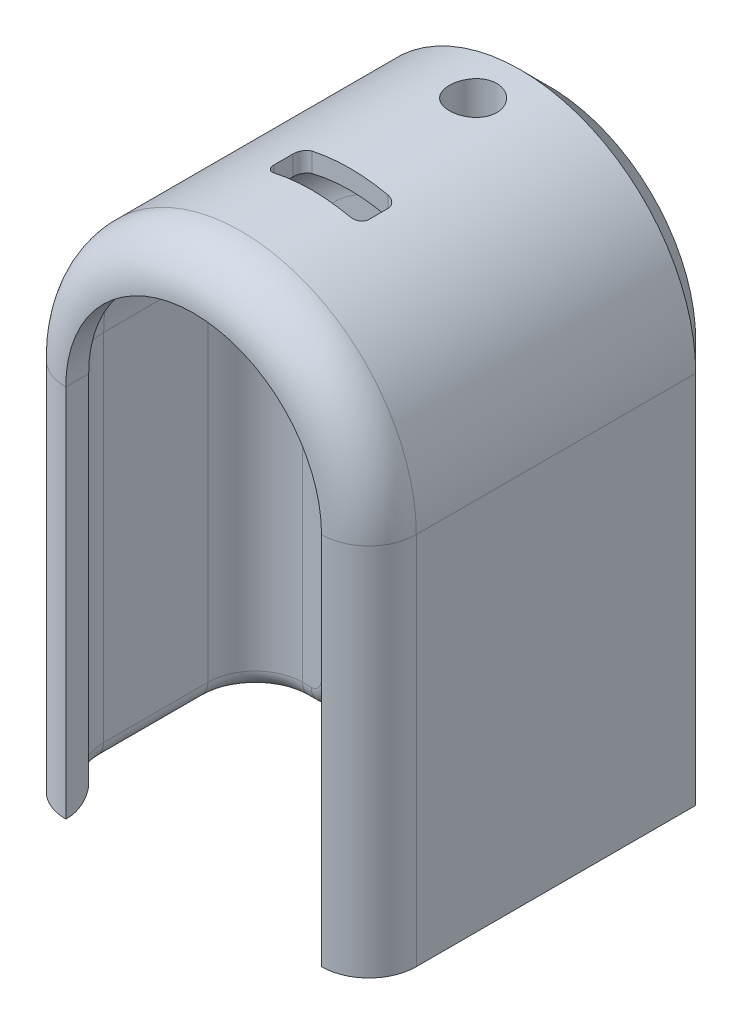
SolidWorks part; units mm, degrees
ref_plane "Plan de face" through (0, 0, 0) normal (0, 0, 1) x (1, 0, 0)
ref_plane "Plan de dessus" through (0, 0, 0) normal (0, 1, 0) x (1, 0, 0)
ref_plane "Plan de droite" through (0, 0, 0) normal (1, 0, 0) x (0, 0, -1)
sketch "Esquisse1" plane through (0, 0, 0) normal (0, 0, 1) x (1, 0, 0)
  line L1 (0, 0) -> (33, 0)
  line L2 (0, 0) -> (0, 39.5)
  line L3 (0, 39.5) -> (33, 39.5)
  line L4 (33, 0) -> (33, 39.5)
  circle A0 centre (16.5, 39.5) radius 16.5
  dimension "D1" = 33
  dimension "D2" = 39.5
extrude "Boss.-Extru.1" add sketch "Esquisse1" along normal blind 21 contours L3 A0 | L3 A0 | A0 L2 L1 L4
shell "Coque2" thickness 2
fillet "Congé1" radius 5 6 edges at (33, 19.75, 0) (0, 19.75, 0) (33, 19.75, 21) (0, 19.75, 21) (16.5, 56, 0) (16.5, 56, 21)
sketch "Esquisse2" plane through (0, 0, 23) normal (0, 0, 1) x (1, 0, 0)
  line L0 (35, 0) -> (35, 39.5) construction
  line L1 (-2, 0) -> (-2, 39.5) construction
  line L2 (35, 0) -> (35, 39.5)
  line L3 (-2, 0) -> (-2, 39.5)
  line L4 (3, 0) -> (3, 39.5)
  line L5 (30, 0) -> (30, 39.5)
  line L6 (3, 0) -> (30, 0)
  arc A0 (35, 39.5) -> (-2, 39.5) centre (16.5, 39.5) ccw construction
  arc A1 (35, 39.5) -> (-2, 39.5) centre (16.5, 39.5) ccw
  arc A2 (30, 39.5) -> (3, 39.5) centre (16.5, 39.5) ccw
  line M4 (-2, 0) -> (35, 0)
  dimension "D1" = 5
extrude "Enlèv. mat.-Extru.1" cut sketch "Esquisse2" against normal blind 10 contours L5 A2 L4 M4
fillet "Congé3" radius 5 3 edges at (35, 19.75, 23) (16.5, 58, 23) (-2, 19.75, 23)
sketch "Esquisse3" plane through (0, 0, -2) normal (0, 0, -1) x (-1, 0, 0)
  line L0 (-16.5, 15) -> (-16.5, 14) construction
  line L1 (-11.4973, 15) -> (-11.4973, 14)
  line L2 (-21.5027, 15) -> (-21.5027, 14)
  line L3 (-16.5, 26.5) -> (-16.5, 27.5) construction
  line L4 (-21.5, 26.5) -> (-21.5, 27.5)
  line L5 (-11.5, 26.5) -> (-11.5, 27.5)
  circle A0 centre (-16.5, 26.5) radius 5
  circle A1 centre (-16.5, 15) radius 5
  arc A2 (0, 39.5) -> (-33, 39.5) centre (-16.5, 39.5) ccw construction
  arc A3 (-11.4973, 15) -> (-21.5027, 15) centre (-16.5, 15) ccw
  arc A4 (-21.5027, 14) -> (-11.4973, 14) centre (-16.5, 14) ccw
  arc A5 (-21.5, 26.5) -> (-11.5, 26.5) centre (-16.5, 26.5) ccw
  arc A6 (-11.5, 27.5) -> (-21.5, 27.5) centre (-16.5, 27.5) ccw
  point P7 (-16.5, 56)
  point P8 (-16.5, 14.5)
  point P9 (-16.5, 15)
  point P10 (-16.5, 26.5)
  point P16 (-16.5, 27)
  dimension "D1" = 10
  dimension "D2" = 10
  dimension "D5" = 5
  dimension "D6" = 1
  dimension "D3" = 29.5
  dimension "D4" = 11.5
  dimension "D7" = 1
extrude "Enlèv. mat.-Extru.2" cut sketch "Esquisse3" against normal blind 10 contours L2 A4 L1 A3 A1 | A0 | L5 A6 L4 A0
sketch "Esquisse4" plane through (0, 0, 0) normal (0, -1, 0) x (-1, 0, 0)
  line L1 (-11.5, -10.5) -> (-21.5, -10.5)
  line L2 (-11.5, -10.5) -> (-11.5, -6.5)
  line L3 (-11.5, -6.5) -> (-21.5, -6.5)
  line L4 (-21.5, -10.5) -> (-21.5, -6.5)
  line L5 (-30, -23) -> (-3, -23) construction
  point P4 (-16.5, -10.5)
  point P7 (-16.5, -23)
  point P12 (-35.1083, -10.5)
  point P13 (-35.1083, -10.5)
  dimension "D1" = 4
  dimension "D2" = 10
  dimension "D3" = 0
extrude "Enlèv. mat.-Extru.4" cut sketch "Esquisse4" against normal through all
fillet "Congé5" radius 1 4 edges at (21.5, 56.2678, 6.5) (11.5, 56.2678, 10.5) (11.5, 56.2678, 6.5) (21.5, 56.2678, 10.5)
sketch "Esquisse6" plane through (0, 0, -2) normal (0, 0, -1) x (-1, 0, 0)
  line L0 (2, 0) -> (-35, 0) construction
  circle A0 centre (-16.5, 0) radius 8
  dimension "D1" = 16
extrude "Enlèv. mat.-Extru.6" cut sketch "Esquisse6" against normal blind 10
fillet "Congé7" radius 3 2 edges at (8.5, 0, -1) (24.5, 0, -1)
fillet "Congé8" radius 2 11 edges at (0.8167, 0, 18.7386) (32.1833, 0, 18.7386) (33, 0, 10.5) (31.5355, 0, 1.4645) (25.2739, 0.6068, 0) (16.5, 8, 0) (7.7261, 0.6068, 0) (1.4645, 0, 1.4645) (0, 0, 10.5) (27.5415, 0, 0) (5.4585, 0, 0)
sketch "Esquisse15" plane through (0, 0, -2) normal (0, 0, -1) x (-1, 0, 0)
  line L0 (2, 14.2) -> (-1.4, 14.2)
  line L1 (-1.4, 14.2) -> (-1.4, 9.4)
  line L2 (-1.4, 9.4) -> (-4.2, 9.4)
  line L3 (-4.2, 9.4) -> (-4.2, 14.2)
  line L4 (-4.2, 14.2) -> (-11.4973, 14.2)
  line L5 (-11.4973, 15) -> (-11.4973, 14) construction
  line L6 (-28, 0) -> (-27.083, 0)
  line L7 (-5.917, 0) -> (-5, 0)
  line L8 (-5, 0) -> (2, 0)
  line L9 (2, 0) -> (2, 39.5)
  line L10 (-35, 39.5) -> (-35, 0)
  line L11 (-35, 0) -> (-28, 0)
  line L12 (-28, 0) -> (-27.083, 0)
  line L13 (-5.917, 0) -> (-5, 0)
  line L14 (-5, 0) -> (2, 0)
  line L15 (2, 14.2) -> (2, 0)
  line L16 (-35, 39.5) -> (-35, 0)
  line L17 (-35, 0) -> (-28, 0)
  line L18 (-11.4973, 14) -> (-11.4973, 14.2)
  line L19 (-21.5027, 14) -> (-21.5, 27)
  line L20 (-8.6, 32.5) -> (-8.6, 37.1)
  line L21 (2, 37.1) -> (2, 14.2) construction
  line L22 (-8.6, 37.1) -> (-4.2, 37.1)
  line L23 (-4.2, 37.1) -> (-4.2, 41.9)
  line L24 (-4.2, 41.9) -> (-1.35, 41.9)
  line L25 (-1.35, 41.9) -> (-1.35, 37.1)
  line L26 (-1.35, 37.1) -> (2, 37.1)
  line L27 (2, 39.5) -> (2, 37.1)
  line L28 (-21.5, 26.5) -> (-21.5, 27.5) construction
  line L29 (-8.6, 32.5) -> (-16.5, 32.5)
  line L30 (-21.5, 27) -> (-21.5, 27.5)
  arc A0 (-21.5027, 14) -> (-11.4973, 14) centre (-16.5, 14) ccw construction
  arc A1 (-21.5027, 14) -> (-11.4973, 14) centre (-16.5, 14) ccw
  arc A2 (-11.5, 27.5) -> (-21.5, 27.5) centre (-16.5, 27.5) ccw construction
  arc A3 (-11.5, 27.5) -> (-21.5, 27.5) centre (-16.5, 27.5) ccw
  arc A4 (-27.083, 0) -> (-24.1967, 2.1818) centre (-27.083, 3) ccw
  arc A5 (-27.083, 0) -> (-24.1967, 2.1818) centre (-27.083, 3) ccw
  arc A6 (-8.8033, 2.1818) -> (-5.917, 0) centre (-5.917, 3) ccw
  arc A7 (2, 39.5) -> (-35, 39.5) centre (-16.5, 39.5) ccw
  arc A8 (-8.8033, 2.1818) -> (-24.1967, 2.1818) centre (-16.5, 0) ccw
  arc A9 (-8.8033, 2.1818) -> (-24.1967, 2.1818) centre (-16.5, 0) ccw
  arc A10 (-8.8033, 2.1818) -> (-5.917, 0) centre (-5.917, 3) ccw
  arc A11 (2, 39.5) -> (-35, 39.5) centre (-16.5, 39.5) ccw
  point P23 (-21.5013, 20.5)
  dimension "D2" = 4.4
  dimension "D3" = 3.4
  dimension "D4" = 2.8
  dimension "D5" = 4.8
  dimension "D6" = 0
  dimension "D7" = 6.3
  dimension "D8" = 22.9
  dimension "D9" = 4.8
  dimension "D10" = 2.85
  dimension "D11" = 4.8
  dimension "D14" = 3.35
  dimension "D1" = 0
extrude "Boss.-Extru.4" add sketch "Esquisse15" along normal blind 12.5
sketch "Esquisse16" plane through (-2, 0, 0) normal (-1, 0, 0) x (0, 0, 1)
  circle A0 centre (-8.1, 39.75) radius 1
  circle A1 centre (-8.1, 11.7639) radius 1
  dimension "D1" = 2
  dimension "D2" = 2
extrude "Enlèv. mat.-Extru.7" cut sketch "Esquisse16" against normal blind 9
sketch "Esquisse17" plane through (-2, 0, 0) normal (-1, 0, 0) x (0, 0, 1)
  circle A0 centre (-8.1, 11.7639) radius 1.5
  circle A1 centre (-8.1, 39.75) radius 1.5
  dimension "D1" = 3
  dimension "D2" = 3
extrude "Enlèv. mat.-Extru.8" cut sketch "Esquisse17" against normal blind 2
sketch "Esquisse18" plane through (0, 0, -14.5) normal (0, 0, -1) x (-1, 0, 0)
  line L1 (-31.5012, 10.341) -> (-23.5012, 10.341)
  line L2 (-31.5012, 10.341) -> (-31.5012, 41.341)
  line L3 (-31.5012, 41.341) -> (-23.5012, 41.341)
  line L4 (-23.5012, 10.341) -> (-23.5012, 41.341)
  line L5 (-21.5024, 15.0463) -> (-21.5, 27) construction
  point P6 (-21.5012, 21.0231)
  point P7 (-23.5012, 25.841)
  dimension "D1" = 31
  dimension "D2" = 8
  dimension "D3" = 2
  dimension "D4" = 0
extrude "Enlèv. mat.-Extru.9" cut sketch "Esquisse18" against normal blind 14
sketch "Esquisse19" plane through (0, 0, 0) normal (0, -1, 0) x (-1, 0, 0)
  line L0 (-35, 14.5) -> (-27.083, 14.5) construction
  line L1 (-28.5012, 14.5) -> (-30.5012, 14.5)
  line L2 (-28.5012, 14.5) -> (-28.5012, 4.5)
  line L3 (-28.5012, 4.5) -> (-30.5012, 4.5)
  line L4 (-30.5012, 14.5) -> (-30.5012, 4.5)
  line L5 (-31.5012, 14.5) -> (-23.5012, 14.5) construction
  point P6 (-29.5012, 14.5)
  point P9 (-27.5012, 14.5)
  dimension "D1" = 2
  dimension "D2" = 2
  dimension "D3" = 10
chamfer "Chanfrein1" distance 3 angle 45 4 edges at (-2, 38.3, -14.5) (16.5, 58, -14.5) (35, 19.75, -14.5) (-2, 7.1, -14.5)
sketch "Esquisse21" plane through (0, 0, -14.5) normal (0, 0, -1) x (-1, 0, 0)
  circle A0 centre (-4.5, 5) radius 1.1
  circle A1 centre (-28.5, 5) radius 1.1
  circle A2 centre (-16.5897, 35.5) radius 1.1
  arc A3 (-11.4973, 15) -> (-21.5024, 15.0463) centre (-16.5, 15) ccw construction
  dimension "D1" = 2.2
  dimension "D2" = 2.2
  dimension "D3" = 2.2
  dimension "D4" = 12
  dimension "D5" = 12
  dimension "D6" = 3
  dimension "D7" = 10
  dimension "D8" = 10
sketch "Esquisse22" plane through (0, 0, -14.5) normal (0, 0, -1) x (-1, 0, 0)
  line L0 (-8.6, 32.5) -> (-16.5, 32.5) construction
  circle A0 centre (-16.5897, 40.5) radius 5.25
  dimension "D3" = 10.5
  dimension "D1" = 8
extrude "Enlèv. mat.-Extru.11" cut sketch "Esquisse22" against normal blind 10.5
sketch "Esquisse28" plane through (0, 0, -14.5) normal (0, 0, -1) x (-1, 0, 0)
  line L0 (-23.5012, 10.341) -> (-23.5012, 41.341) construction
  line L1 (-16.5897, 35.25) -> (-23.5012, 35.25)
  line L2 (-16.5897, 35.25) -> (-16.5897, 41.1397)
  line L3 (-16.5897, 41.1397) -> (-23.5012, 41.1397)
  line L4 (-23.5012, 35.25) -> (-23.5012, 41.1397)
  circle A0 centre (-16.5897, 40.5) radius 5.25 construction
extrude "Enlèv. mat.-Extru.15" cut sketch "Esquisse28" against normal blind 10
sketch "Esquisse29" plane through (0, 41.341, 0) normal (0, -1, 0) x (-1, 0, 0)
  circle A0 centre (-16.5, 6.5) radius 2.5
  dimension "D3" = 5
  dimension "D1" = 8
  dimension "D2" = 0
extrude "Enlèv. mat.-Extru.16" cut sketch "Esquisse29" against normal blind 28
